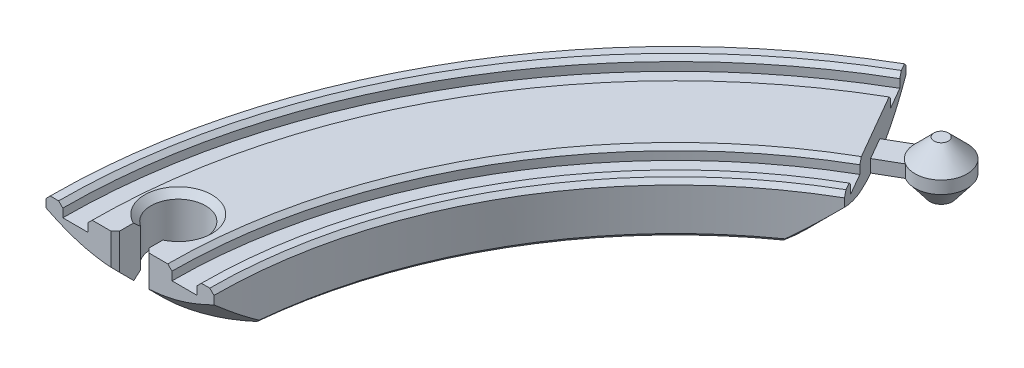
SolidWorks part; units mm, degrees
ref_plane "Front Plane" through (0, 0, 0) normal (0, 0, 1) x (1, 0, 0)
ref_plane "Top Plane" through (0, 0, 0) normal (0, 1, 0) x (1, 0, 0)
ref_plane "Right Plane" through (0, 0, 0) normal (1, 0, 0) x (0, 0, -1)
sketch "Sketch2" plane through (0, 0, 0) normal (0, 0, 1) x (1, 0, 0)
  line L0 (-20, 0) -> (20, 0)
  line L1 (20, 0) -> (20, 12)
  line L2 (20, 12) -> (16, 12)
  line L3 (16, 12) -> (16, 9)
  line L4 (16, 9) -> (10, 9)
  line L5 (10, 9) -> (10, 12)
  line L6 (10, 12) -> (-10, 12)
  line L7 (-10, 12) -> (-10, 9)
  line L8 (-10, 9) -> (-16, 9)
  line L9 (-16, 9) -> (-16, 12)
  line L10 (-16, 12) -> (-20, 12)
  line L11 (-20, 12) -> (-20, 0)
  line L12 (129.9038, 0) -> (129.9038, 12)
  point P4 (0, 0)
  dimension "D1" = 40
  dimension "D2" = 12
  dimension "D3" = 3
  dimension "D4" = 4
  dimension "D5" = 6
  dimension "D6" = 129.9038
revolve "Revolve1" add sketch "Sketch2" angle 60 about L12 region at (0, 5.6351, 0) reverse direction yes
sketch "Sketch3" plane through (0, 12, 0) normal (0, 1, 0) x (1, 0, 0)
  line L0 (10, 0) -> (-10, 0) construction
  line L2 (-3.5, 0) -> (3.5, 0)
  line L3 (-3.5, 0) -> (-3.5, 11.5)
  line L4 (-3.5, 11.5) -> (3.5, 11.5)
  line L5 (3.5, 0) -> (3.5, 11.5)
  line L6 (-3.5, 0) -> (3.5, 11.5) construction
  line L7 (-3.5, 11.5) -> (3.5, 0) construction
  circle A0 centre (0, 11.5) radius 6.5
  point P4 (0, 5.75)
  point P10 (0, 0)
  line M6 (-10, 0) -> (10, 0)
  dimension "D1" = 13
  dimension "D2" = 11.5
  dimension "D3" = 7
extrude "Cut-Extrude1" cut sketch "Sketch3" against normal through all contours L5 A0 L3 L4 | L3 A0 L5 L4 | A0 L3 L5 M6 region at (0, 12, -2.6732) region at (0, 12, -12.9919) region at (0, 12, -8.4074)
sketch "Sketch4" plane through (0, 12, 0) normal (0, 1, 0) x (1, 0, 0)
  line L0 (66.4519, 109.9019) -> (63.4519, 115.0981)
  line L1 (66.4519, 109.9019) -> (76.4112, 115.6519)
  line L2 (63.4519, 115.0981) -> (73.4112, 120.8481)
  line L3 (76.4112, 115.6519) -> (73.4112, 120.8481)
  line L4 (69.9519, 103.8397) -> (59.9519, 121.1603) construction
  circle A0 centre (74.9112, 118.25) radius 6.2
  point P9 (64.9519, 112.5)
  line M6 (69.9519, 103.8397) -> (59.9519, 121.1603)
  dimension "D1" = 12.4
  dimension "D2" = 6
  dimension "D3" = 11.5
extrude "Boss-Extrude1" add sketch "Sketch4" against normal up to surface (12 mm away) contours L1 A0 L2 L3 | L2 A0 L1 L3 region at (72.3315, 12, -116.7606) region at (75.9935, 12, -118.8749) up to face at (12.4699, 0, -33.3033)
extrude "Boss-Extrude2" add sketch "Sketch4<3>" against normal blind 7.5 contours A0 L2 L1 M6 region at (67.3597, 12, -113.8902)
sketch "Sketch4<3>" plane through (0, 12, 0) normal (0, 1, 0) x (1, 0, 0) same geometry as "Sketch4"
extrude "Cut-Extrude2" cut sketch "Sketch4<5>" against normal blind 4.5 contours A0 L2 L1 M6 region at (67.3597, 12, -113.8902)
sketch "Sketch4<5>" plane through (0, 12, 0) normal (0, 1, 0) x (1, 0, 0) same geometry as "Sketch4"
chamfer "Chamfer2" distance 4.5 angle 45 1 edges at (68.7112, 12, -118.25)
chamfer "Chamfer5" distance 3.5 distance2 4.5 1 edges at (74.9112, 0, -124.45) first distance on face at (74.9112, 0, -124.45)
chamfer "Chamfer3" distance 1.5 angle 45 2 edges at (0, 0, -18) (0, 12, -18)
sketch "Sketch17" plane through (-33.976, 0, -58.8481) normal (-0.5, 0, -0.866) x (-0.866, 0, 0.5)
  line L0 (-118.5741, 10.5741) -> (-118.5741, 0)
  line L1 (-118.5741, 0) -> (-108, 0)
  line L2 (-108, 0) -> (-118.5741, 10.5741)
  line L4 (-83, -1.2652) -> (-83, 10.5741) construction
  dimension "D1" = 25
revolve "Cut-Revolve1" cut sketch "Sketch17" angle 90 about L4
ref_plane "Plane1" through (-32.476, 0, -56.25) normal (-0.5, 0, -0.866) x (-0.866, 0, 0.5)
mirror "Mirror1" about plane through (-32.476, 0, -56.25) normal (-0.5, 0, -0.866) of "Cut-Revolve1"
chamfer "Chamfer4" distance 4.5 angle 45 1 edges at (64.9519, 0, -112.5)
ref_plane "Plane2" through (32.476, 0, -56.25) normal (0.5, 0, -0.866) x (-0.866, 0, -0.5)
mirror "Mirror4" about plane through (32.476, 0, -56.25) normal (0.5, 0, -0.866) of "Cut-Revolve1", "Mirror1"
chamfer "Chamfer1" distance 1 angle 45 10 edges at (34.7243, 12, -54.9519) (31.2602, 12, -56.9519) (26.0641, 12, -59.9519) (8.7436, 12, -69.9519) (3.5474, 12, -72.9519) (0.0833, 12, -74.9519) (34.7243, 0, -54.9519) (0.0833, 0, -74.9519) (3.5, 8.2521, 0) (-3.5, 8.2521, 0)
